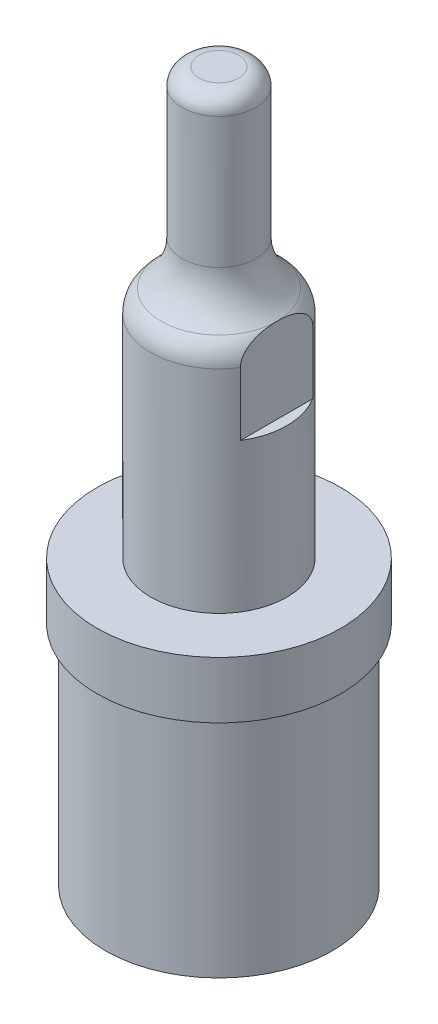
SolidWorks part; units mm, degrees
ref_plane "Front Plane" through (0, 0, 0) normal (0, 0, 1) x (1, 0, 0)
ref_plane "Top Plane" through (0, 0, 0) normal (0, 1, 0) x (1, 0, 0)
ref_plane "Right Plane" through (0, 0, 0) normal (1, 0, 0) x (0, 0, -1)
sketch "Sketch1" plane through (0, 0, 0) normal (0, 1, 0) x (1, 0, 0)
  circle A0 centre (0, 0) radius 20
  dimension "D1" = 40
extrude "Boss-Extrude1" add sketch "Sketch1" along normal blind 40
sketch "Sketch2" plane through (0, 40, 0) normal (0, 1, 0) x (1, 0, 0)
  circle A0 centre (0, 0) radius 21.5
  dimension "D1" = 43
extrude "Boss-Extrude2" add sketch "Sketch2" along normal blind 10
sketch "Sketch3" plane through (0, 50, 0) normal (0, 1, 0) x (1, 0, 0)
  circle A0 centre (0, 0) radius 6.5
  dimension "D1" = 13
extrude "Boss-Extrude3" add sketch "Sketch3" along normal blind 75
sketch "Sketch4" plane through (0, 50, 0) normal (0, 1, 0) x (1, 0, 0)
  circle A0 centre (0, 0) radius 12
  dimension "D1" = 24
extrude "Boss-Extrude4" add sketch "Sketch4" along normal blind 40
fillet "Fillet1" radius 10 1 edges at (0, 90, 6.5)
fillet "Fillet2" radius 5 1 edges at (0, 90, 12)
fillet "Fillet3" radius 3 1 edges at (0, 125, 6.5)
sketch "Sketch5" plane through (0, 0, 0) normal (0, -1, 0) x (1, 0, 0)
  circle A0 centre (0, 0) radius 4
  dimension "D1" = 8
extrude "Boss-Extrude5" add sketch "Sketch5" along normal blind 5
sketch "Sketch6" plane through (0, 0, 0) normal (0, 0, 1) x (1, 0, 0)
  line L0 (-12, 87.3221) -> (-12, 50) construction
  line L1 (-10.1667, 91.1915) -> (-12, 91.1915)
  line L2 (-10.1667, 91.1915) -> (-10.1667, 76.1915)
  line L3 (-10.1667, 76.1915) -> (-12, 76.1915)
  line L4 (-12, 91.1915) -> (-12, 76.1915)
  line L5 (0, -23.65) -> (0, 23.65) construction
  line L6 (12, 91.1915) -> (12, 76.1915)
  line L7 (10.1667, 76.1915) -> (12, 76.1915)
  line L8 (10.1667, 91.1915) -> (10.1667, 76.1915)
  line L9 (10.1667, 91.1915) -> (12, 91.1915)
  dimension "D1" = 15
extrude "Cut-Extrude1" cut sketch "Sketch6" against normal through all both and the other way through all
